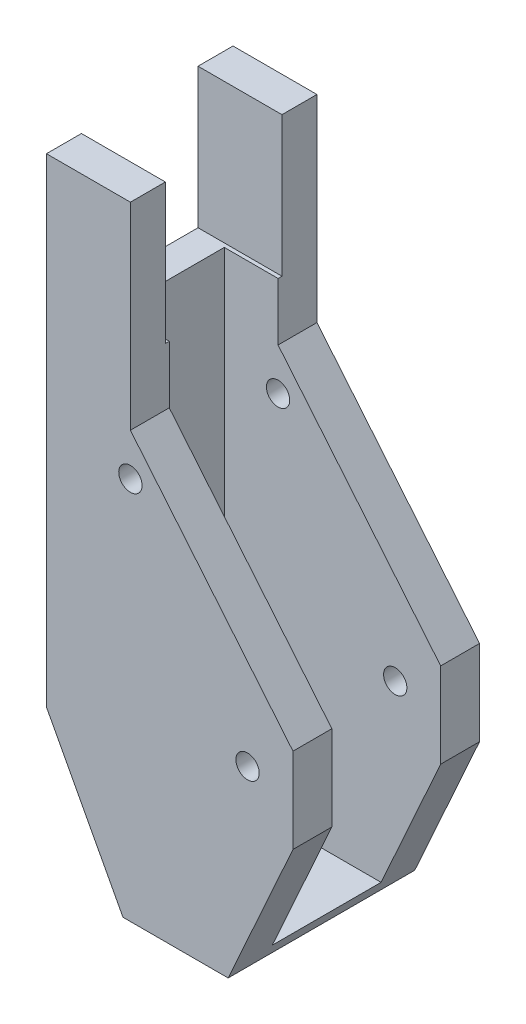
SolidWorks part; units mm, degrees
ref_plane "前视基准面" through (0, 0, 0) normal (0, 0, 1) x (1, 0, 0)
ref_plane "上视基准面" through (0, 0, 0) normal (0, 1, 0) x (1, 0, 0)
ref_plane "右视基准面" through (0, 0, 0) normal (1, 0, 0) x (0, 0, -1)
sketch "草图1" plane through (0, 0, 0) normal (0, 0, 1) x (1, 0, 0)
  line L8 (-29.8155, -4.2167) -> (49970.1845, -4.2167) construction
  line L9 (-29.8155, -28.7167) -> (49970.1845, -28.7167) construction
  line L10 (-8.8963, -4.2167) -> (26190.399, -42590.5634) construction
  line L20 (-8.8963, -35.0463) -> (-8.8963, 49964.9537) construction
  line L21 (-29.8155, -35.0463) -> (12.023, -35.0463)
  line L22 (-29.8155, -35.0463) -> (-29.8155, 26.613)
  line L23 (-29.8155, 26.613) -> (12.023, 26.613)
  line L24 (12.023, -35.0463) -> (12.023, 26.613)
  circle A0 centre (-8.8963, -4.2167) radius 1.5
  circle A1 centre (6.1762, -28.7167) radius 1.5
  point P5 (-29.8155, -4.2167)
  point P9 (-8.8963, -35.0463)
  dimension "D1" = 24.5
  dimension "D2" = 3
  dimension "D6" = 121.6
  dimension "D3" = 20.9193
  dimension "D7" = 3
  dimension "D4" = 61.6593
  dimension "D5" = 41.8385
extrude "凸台-拉伸1" add sketch "草图1" along normal blind 24
shell "抽壳2" thickness 5 removed face at (-8.8963, -35.0463, 12) removed face at (12.023, -4.2167, 12) removed face at (-8.8963, 26.613, 12)
sketch "草图7" plane through (12.023, 0, 0) normal (1, 0, 0) x (0, 0, -1)
  line L1 (-19, 26.613) -> (-5, 26.613)
  line L2 (-19, 26.613) -> (-19, -35.0463)
  line L3 (-19, -35.0463) -> (-5, -35.0463)
  line L4 (-5, 26.613) -> (-5, -35.0463)
  dimension "D1" = 61.6593
  dimension "D2" = 14
extrude "切除-拉伸2" cut sketch "草图7" against normal blind 38
sketch "草图11" plane through (-29.8155, 0, 0) normal (-1, 0, 0) x (0, 0, 1)
  line L1 (19, 26.613) -> (5, 26.613)
  line L2 (19, 26.613) -> (19, -35.0463)
  line L3 (19, -35.0463) -> (5, -35.0463)
  line L4 (5, 26.613) -> (5, -35.0463)
  dimension "D1" = 61.6593
  dimension "D2" = 14
extrude "凸台-拉伸2" add sketch "草图11" against normal blind 14
sketch "草图12" plane through (0, 0, 24) normal (0, 0, 1) x (1, 0, 0)
  line L1 (-29.8155, 26.613) -> (-19.6941, 26.613)
  line L2 (-29.8155, 26.613) -> (-29.8155, -35.0463)
  line L3 (-29.8155, -35.0463) -> (-19.6941, -35.0463)
  line L4 (-19.6941, 26.613) -> (-19.6941, -35.0463)
  line L5 (-29.8155, -35.0463) -> (12.023, -35.0463) construction
  dimension "D1" = 61.6593
  dimension "D2" = 10.1214
extrude "切除-拉伸3" cut sketch "草图12" against normal through all
sketch "草图17" plane through (0, 0, 24) normal (0, 0, 1) x (1, 0, 0)
  line L0 (-8.8963, -4.2167) -> (-8.8963, 49995.7833) construction
  line L1 (-8.8963, 26.613) -> (-8.8963, 1.1974)
  line L2 (12.023, 26.613) -> (-19.6941, 26.613) construction
  line L3 (-8.8963, 1.1974) -> (12.023, -24.0972)
  line L4 (12.023, -35.0463) -> (12.023, 26.613) construction
  line L5 (12.023, -24.0972) -> (12.023, 26.613)
  line L6 (12.023, 26.613) -> (-8.8963, 26.613)
extrude "切除-拉伸5" cut sketch "草图17" against normal through all
sketch "草图18" plane through (-19.6941, 0, 0) normal (-1, 0, 0) x (0, 0, 1)
  line L0 (0, 26.613) -> (24, 26.613) construction
  line L1 (4.5, 26.613) -> (19.5, 26.613)
  line L2 (4.5, 26.613) -> (4.5, 8.613)
  line L3 (4.5, 8.613) -> (19.5, 8.613)
  line L4 (19.5, 26.613) -> (19.5, 8.613)
  line L5 (0, -35.0463) -> (0, 26.613) construction
  line L6 (24, -35.0463) -> (24, 26.613) construction
  dimension "D1" = 18
  dimension "D2" = 15
  dimension "D3" = 4.5
  dimension "D4" = 4.5
extrude "切除-拉伸6" cut sketch "草图18" against normal through all
sketch "草图20" plane through (0, 0, 24) normal (0, 0, 1) x (1, 0, 0)
  line L0 (-19.6941, -35.0463) -> (-9.8535, -53.541)
  line L1 (-9.8535, -53.541) -> (3.6836, -53.541)
  line L2 (3.6836, -53.541) -> (12.023, -35.0463)
  line L3 (12.023, -35.0463) -> (-19.6941, -35.0463)
extrude "凸台-拉伸5" add sketch "草图20" against normal blind 24
sketch "草图22" plane through (0, -35.0463, 0) normal (0, 1, 0) x (1, 0, 0)
  line L1 (-15.8155, -5) -> (12.023, -5)
  line L2 (-15.8155, -5) -> (-15.8155, -19)
  line L3 (-15.8155, -19) -> (12.023, -19)
  line L4 (12.023, -5) -> (12.023, -19)
  dimension "D1" = 14
  dimension "D2" = 27.8385
extrude "切除-拉伸8" cut sketch "草图22" against normal blind 17
ref_plane "基准面4" through (-29.8818, -15.8995, 0) normal (0.8828, 0.4697, 0) x (0, 0, -1)
sketch "草图23" plane through (-29.8818, -15.8995, 0) normal (0.8828, 0.4697, 0) x (0, 0, -1)
  line L5 (-19.4003, -29.5799) -> (-4.4092, -29.5799)
  line L6 (-19.4003, -29.5799) -> (-19.4003, -41.3133)
  line L7 (-19.4003, -41.3133) -> (-4.4092, -41.3133)
  line L8 (-4.4092, -29.5799) -> (-4.4092, -41.3133)
  dimension "D1" = 11.7334
  dimension "D2" = 14.9912
extrude "凸台-拉伸8" add sketch "草图23" along normal blind 2
fillet "圆角3" radius 4 1 edges at (-14.2217, -41.0735, 12)
